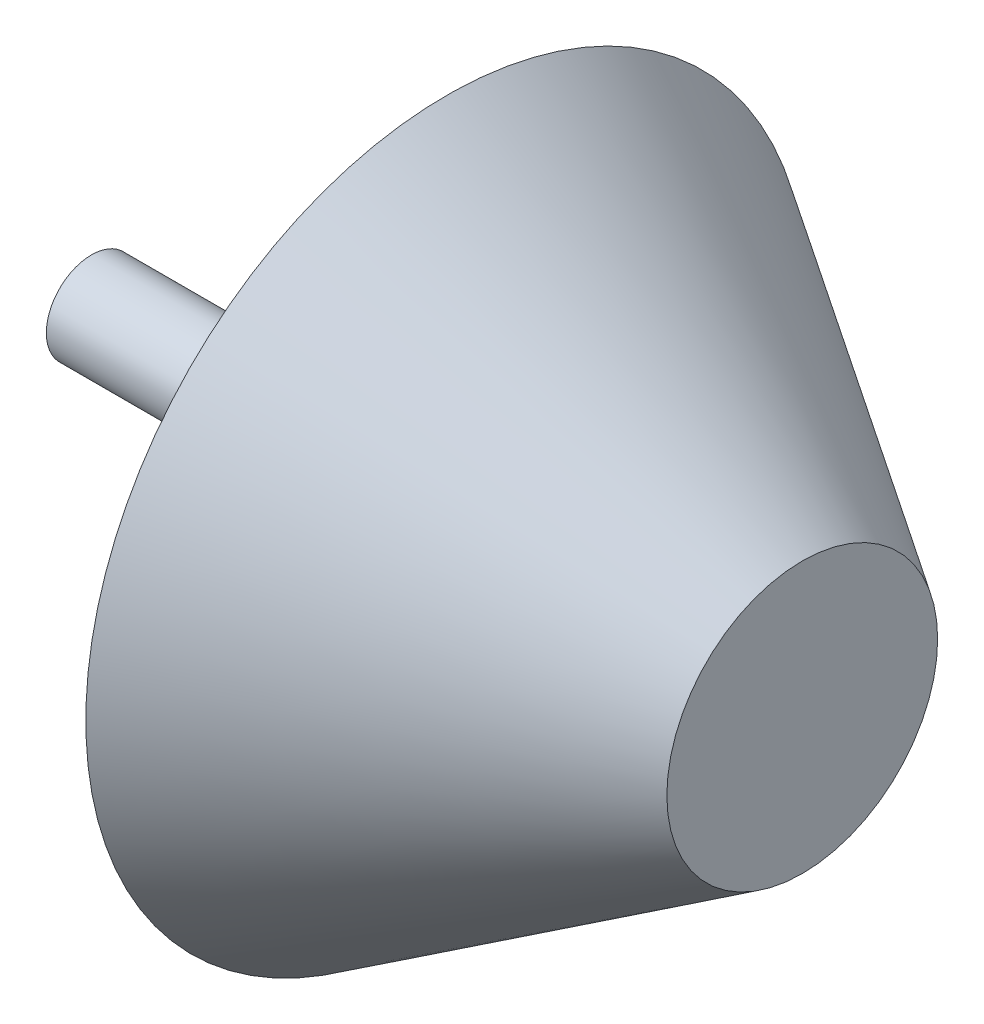
SolidWorks part; units mm, degrees
ref_plane "Front Plane" through (0, 0, 0) normal (1, 0, 0) x (0, 1, 0)
ref_plane "Top Plane" through (0, 0, 0) normal (0, 0, 1) x (0, 1, 0)
ref_plane "Right Plane" through (0, 0, 0) normal (0, 1, 0) x (-1, 0, 0)
sketch "Sketch2" plane through (0, 0, 0) normal (1, 0, 0) x (0, 1, 0)
  circle A0 centre (0, 0) radius 101.6
  dimension "D1" = 203.2
ref_plane "Plane1" through (100, 0, 0) normal (1, 0, 0) x (0, 1, 0)
sketch "Sketch3" plane through (100, 0, 0) normal (1, 0, 0) x (0, 1, 0)
  circle A0 centre (0, 0) radius 38.1
  dimension "D1" = 76.2
loft "Loft1" add profiles "Sketch2", "Sketch3" connector at (0, -17.2793, 100.1199) connector at (100, -5.9365, 37.6347)
sketch "Sketch4" plane through (0, 0, 0) normal (-1, 0, 0) x (0, -1, 0)
  circle A0 centre (0, 0) radius 12.7
  dimension "D1" = 25.4
extrude "Boss-Extrude1" add sketch "Sketch4" along normal blind 100
